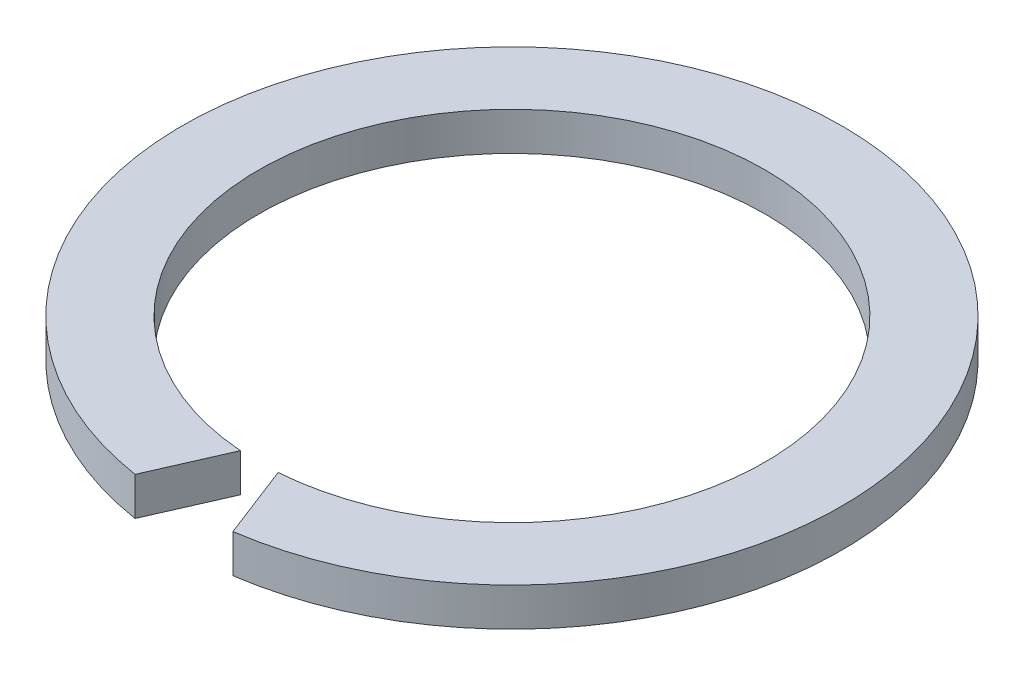
SolidWorks part; units mm, degrees
ref_plane "Front Plane" through (0, 0, 0) normal (0, 0, 1) x (1, 0, 0)
ref_plane "Top Plane" through (0, 0, 0) normal (0, 1, 0) x (1, 0, 0)
ref_plane "Right Plane" through (0, 0, 0) normal (1, 0, 0) x (0, 0, -1)
sketch "Sketch1" plane through (0, 0, 0) normal (0, 1, 0) x (1, 0, 0)
  circle A0 centre (0, 0) radius 16.55
  circle A1 centre (0, 0) radius 21.55
extrude "Boss-Extrude1" add sketch "Sketch1" along normal blind 2.5
sketch "Sketch3" plane through (0, 0, 0) normal (0, 1, 0) x (1, 0, 0)
  line L0 (0, 0) -> (0, -27.1481) construction
  line L1 (-3.9467, -22.6446) -> (3.5965, -22.6446)
  line L2 (0, -15.9363) -> (-1, -15.9363)
  line L3 (0, -15.9363) -> (1, -15.9363)
  line L4 (1, -15.9363) -> (3.5965, -22.6446)
  line L5 (-3.9467, -22.6446) -> (-1, -15.9363)
  point P7 (0, 0)
  point P9 (0, 0)
  point P10 (0, 0)
  point P11 (-0.9938, -15.9363)
  point P12 (-3.9132, -22.5825)
  point P13 (0, 0)
  point P14 (3.6026, -22.6446)
  point P15 (0, 0)
  point P16 (0, 0)
  point P17 (0, 0)
extrude "Cut-Extrude2" cut sketch "Sketch3" against normal blind 12 and the other way blind 15
